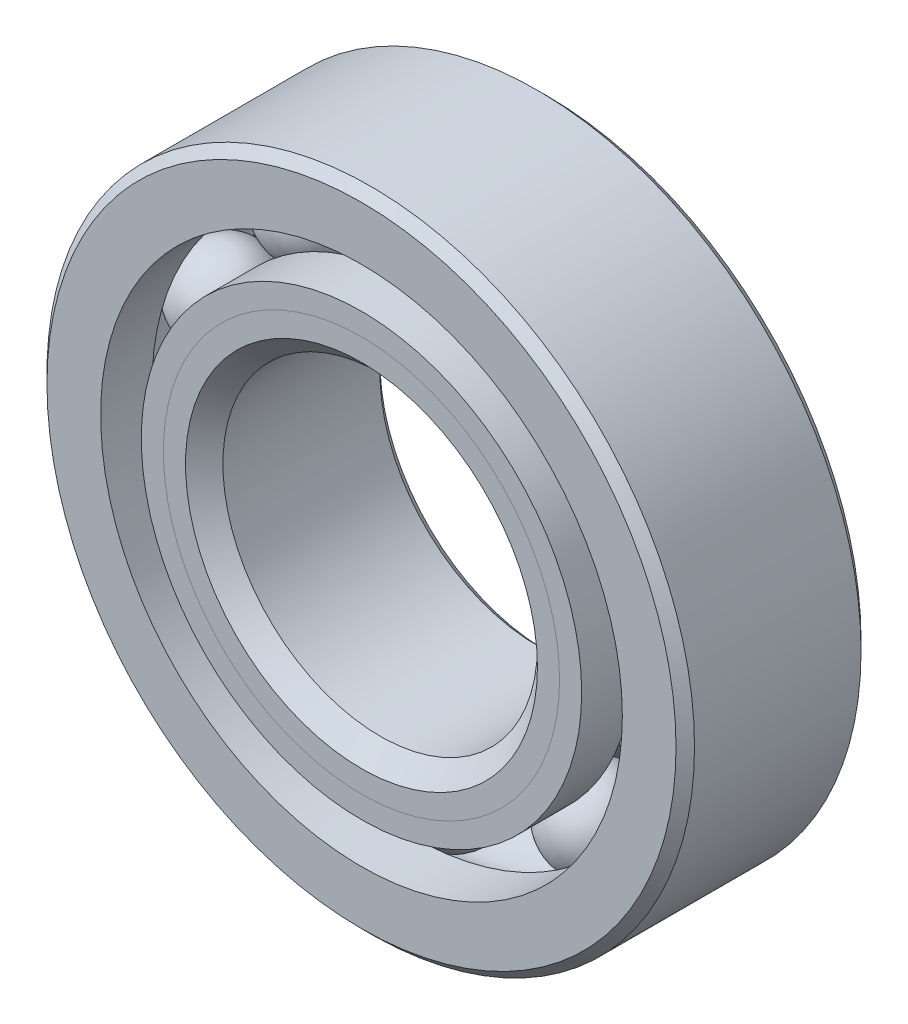
SolidWorks part; units mm, degrees
material "Plain Carbon Steel"
ref_plane "Front Plane" through (0, 0, 0) normal (0, 0, 1) x (1, 0, 0)
ref_plane "Top Plane" through (0, 0, 0) normal (0, 1, 0) x (1, 0, 0)
ref_plane "Right Plane" through (0, 0, 0) normal (1, 0, 0) x (0, 0, -1)
sketch "Sketch1" plane through (0, 0, 0) normal (1, 0, 0) x (0, 0, -1)
  line L0 (-5, 0) -> (5, 0) construction
  line L1 (0, 17.5) -> (0, -17.5) construction
  line L2 (4.5, 17.5) -> (-4.5, 17.5)
  line L3 (-4.5, 17.5) -> (-5, 17)
  line L4 (-5, 17) -> (-5, 14.0989)
  line L5 (-5, 14.0989) -> (-2.2222, 14.0989)
  line L6 (5, 14.0989) -> (2.2222, 14.0989)
  line L7 (5, 17) -> (5, 14.0989)
  line L8 (4.5, 17.5) -> (5, 17)
  line L9 (0, 17.5) -> (0, 13) construction
  line L10 (0, 13) -> (0, 8.5) construction
  arc A0 (-2.2222, 14.0989) -> (2.2222, 14.0989) centre (0, 13) cw
  point P14 (0, 8.5)
  dimension "Width" = 10
  dimension "OD" = 35
  dimension "D1" = 45
  dimension "D2" = 0.5
  dimension "D3" = 4.4444
  dimension "D4" = 1.0989
revolve "Revolve1" add sketch "Sketch1" angle 360 about L0
sketch "Sketch2" plane through (0, 0, 0) normal (1, 0, 0) x (0, 0, -1)
  line L0 (-5, 11.9011) -> (-2.2222, 11.9011)
  line L1 (-5, 17) -> (-5, -17) construction
  line L2 (-5, 11.9011) -> (-5, 10.7058)
  line L3 (-5, 10.7058) -> (-3.8047, 9.5105)
  line L4 (-3.8047, 9.5105) -> (0, 9.5105)
  line L5 (0, 17.5) -> (0, -17.5) construction
  line L6 (0, 9.5105) -> (0, 10.5209)
  line L7 (0, 10.5209) -> (0, 8.5) construction
  line L8 (-5, 11.9011) -> (-5, 9.5105) construction
  line L9 (-5, 9.5105) -> (-3.8047, 9.5105) construction
  arc A0 (-2.2222, 11.9011) -> (0, 10.5209) centre (0, 13) ccw
  arc A1 (2.2222, 14.0989) -> (-2.2222, 14.0989) centre (0, 13) ccw construction
  circle A2 centre (0, 13) radius 2.4791 construction
  dimension "D1" = 45
revolve "Revolve2" add sketch "Sketch2" angle 360 about L0
sketch "Sketch3" plane through (0, 0, 0) normal (1, 0, 0) x (0, 0, -1)
  line L0 (-5, 10.7058) -> (-3.8047, 9.5105)
  line L1 (-3.8047, 9.5105) -> (0, 9.5105)
  line L2 (0, 9.5105) -> (0, 10.5209)
  line L3 (-5, 10.7058) -> (-5, 9.5105)
  line L4 (-5, 11.9011) -> (-5, 9.5105) construction
  line L5 (-5, 9.5105) -> (-3.9895, 8.5)
  line L6 (-3.9895, 8.5) -> (4.5, 8.5)
  line L7 (4.5, 17.5) -> (4.5, -17.5) construction
  line L8 (4.5, 8.5) -> (5, 9)
  line L9 (5, -17) -> (5, 17) construction
  line L10 (5, 9) -> (5, 11.9011)
  line L11 (5, 11.9011) -> (2.2222, 11.9011)
  line L13 (4.5, 17.5) -> (5, 17) construction
  circle A0 centre (0, 13) radius 2.4791 construction
  arc A1 (2.2222, 11.9011) -> (0, 10.5209) centre (0, 13) cw
revolve "Revolve3" add sketch "Sketch3" angle 360 about L0
sketch "Sketch4" plane through (0, 0, 0) normal (1, 0, 0) x (0, 0, -1)
  line L0 (-2.4791, 13) -> (2.4791, 13)
  circle A1 centre (0, 13) radius 2.4791 construction
  arc A2 (-2.4791, 13) -> (2.4791, 13) centre (0, 13) cw
  arc A3 (2.2222, 14.0989) -> (-2.2222, 14.0989) centre (0, 13) ccw construction
revolve "Revolve4" add sketch "Sketch4" angle 360 about L0
ref_axis "Axis1" through (0, 0, -5) along (0, 0, 1)
pattern_circular "CirPattern1" count 10 over 360 about axis through (0, 0, -5) along (0, 0, 1) of bodies 104
equation "\"D2@Sketch1\" = \"Width@Sketch1\"*.05"
equation "\"D3@Sketch1\" = \"Width@Sketch1\"/2.25"
equation "\"D4@Sketch1\" = (((\"OD@Sketch1\"-\"Width@Sketch1\")/2)/3.25)/3.5"
equation "\"D2@CirPattern1\" = 360/\"Balls@CirPattern1\""
